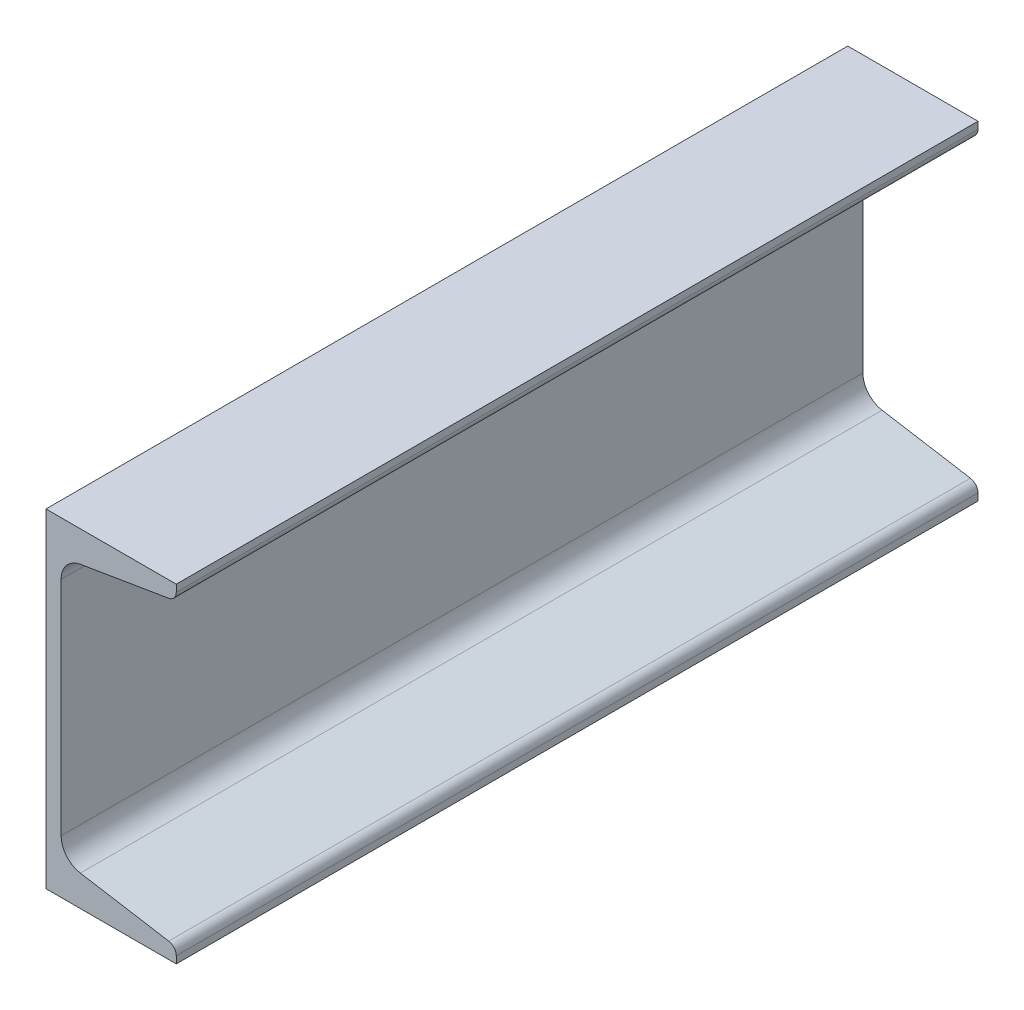
SolidWorks part; units mm, degrees
ref_plane "Front Plane" through (0, 0, 0) normal (0, 0, 1) x (1, 0, 0)
ref_plane "Top Plane" through (0, 0, 0) normal (0, 1, 0) x (1, 0, 0)
ref_plane "Right Plane" through (0, 0, 0) normal (1, 0, 0) x (0, 0, -1)
sketch "Sketch1" plane through (0, 0, 0) normal (0, 0, 1) x (1, 0, 0)
  line L0 (0, 0) -> (0, 101.6)
  line L1 (0, 101.6) -> (40.2336, 101.6)
  line L2 (0, 0) -> (40.2336, 0)
  line L12 (4.6736, 85.0934) -> (4.6736, 16.5066)
  line L15 (40.2336, 101.6) -> (40.2336, 99.412)
  line L16 (40.2336, 0) -> (40.2336, 2.188)
  line L17 (10.6163, 92.1086) -> (37.899, 96.656)
  line L18 (10.6163, 9.4914) -> (37.899, 4.944)
  arc A9 (4.6736, 16.5066) -> (10.6163, 9.4914) centre (11.7856, 16.5066) ccw
  arc A10 (4.6736, 85.0934) -> (10.6163, 92.1086) centre (11.7856, 85.0934) cw
  arc A11 (40.2336, 99.412) -> (37.899, 96.656) centre (37.4396, 99.412) cw
  arc A12 (40.2336, 2.188) -> (37.899, 4.944) centre (37.4396, 2.188) ccw
  dimension "D5" = 7.112
  dimension "D4" = 2.794
  dimension "D6" = 4.6736
  dimension "D2" = 9.463
  dimension "D7" = 2.188
extrude "Boss-Extrude1" add sketch "Sketch1" along normal blind 247.65 contours L0 L1 L15 A11 L17 A10 L12 A9 L18 A12 L16 L2
